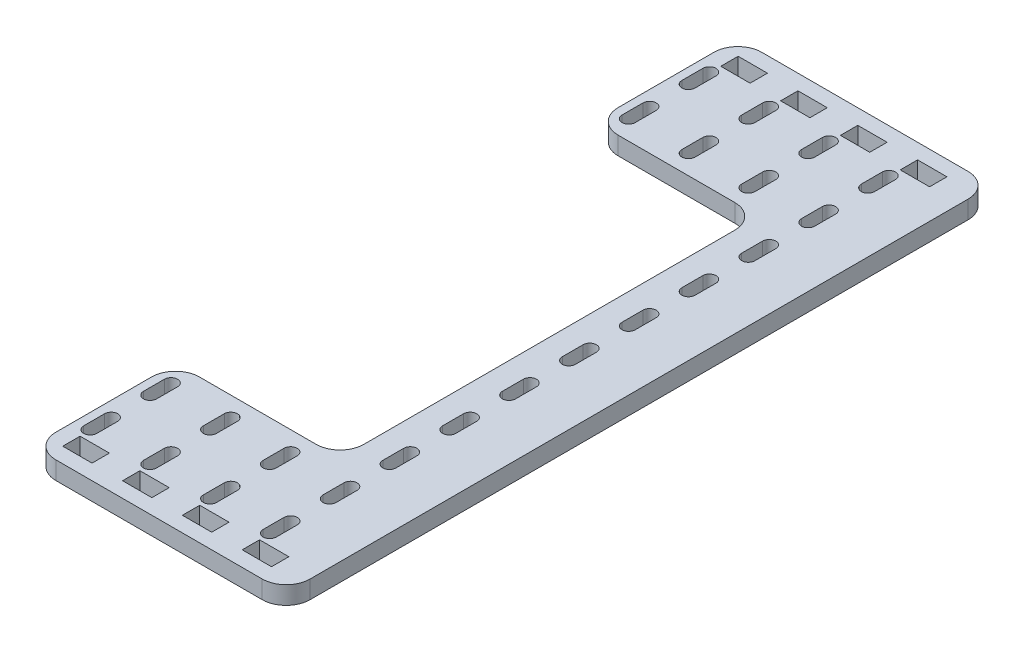
SolidWorks part; units mm, degrees
ref_plane "Front Plane" through (0, 0, 0) normal (0, 0, 1) x (1, 0, 0)
ref_plane "Top Plane" through (0, 0, 0) normal (0, 1, 0) x (1, 0, 0)
ref_plane "Right Plane" through (0, 0, 0) normal (1, 0, 0) x (0, 0, -1)
sketch "Sketch1" plane through (0, 0, 0) normal (0, 1, 0) x (1, 0, 0)
  line L0 (-43.1232, 117.3768) -> (41.8768, 117.3768)
  line L1 (-43.1232, 117.3768) -> (-43.1232, -118.6232)
  line L2 (-43.1232, -118.6232) -> (41.8768, -118.6232)
  line L3 (41.8768, 117.3768) -> (41.8768, -118.6232)
  line L4 (-43.1232, 117.3768) -> (41.8768, -118.6232) construction
  line L5 (-43.1232, -118.6232) -> (41.8768, 117.3768) construction
  point P4 (-0.6232, -0.6232)
extrude "Boss-Extrude1" add sketch "Sketch1" along normal blind 6
sketch "Sketch2" plane through (0, 6, 0) normal (0, 1, 0) x (1, 0, 0)
  line L0 (41.8768, -113.5232) -> (31.8768, -113.5232) construction
  line L1 (41.8768, -118.6232) -> (41.8768, 117.3768) construction
  line L2 (-43.1232, -118.6232) -> (41.8768, -118.6232) construction
  line L3 (11.8768, -107.7232) -> (2.0768, -107.7232)
  line L4 (31.8768, -113.5232) -> (22.0768, -113.5232)
  line L5 (31.8768, -113.5232) -> (31.8768, -107.7232)
  line L6 (31.8768, -107.7232) -> (22.0768, -107.7232)
  line L7 (22.0768, -113.5232) -> (22.0768, -107.7232)
  line L8 (31.8768, -113.5232) -> (22.0768, -107.7232) construction
  line L9 (31.8768, -107.7232) -> (22.0768, -113.5232) construction
  line L10 (2.0768, -113.5232) -> (2.0768, -107.7232)
  line L11 (11.8768, -113.5232) -> (2.0768, -113.5232)
  line L12 (11.8768, -113.5232) -> (11.8768, -107.7232)
  line L13 (-8.1232, -107.7232) -> (-17.9232, -107.7232)
  line L14 (-17.9232, -113.5232) -> (-17.9232, -107.7232)
  line L15 (-8.1232, -113.5232) -> (-17.9232, -113.5232)
  line L16 (-8.1232, -113.5232) -> (-8.1232, -107.7232)
  line L17 (-28.1232, -107.7232) -> (-37.9232, -107.7232)
  line L18 (-37.9232, -113.5232) -> (-37.9232, -107.7232)
  line L19 (-28.1232, -113.5232) -> (-37.9232, -113.5232)
  line L20 (-28.1232, -113.5232) -> (-28.1232, -107.7232)
  point P9 (26.9768, -110.6232)
  dimension "D1" = 10
  dimension "D2" = 5.1
  dimension "D3" = 9.8
  dimension "D4" = 5.8
  dimension "D5" = 4
extrude "Cut-Extrude1" cut sketch "Sketch2" against normal blind 6
ref_plane "Plane1" through (0, 0, 0.6232) normal (0, 0, 1) x (1, 0, 0)
mirror "Mirror2" about plane through (0, 0, 0.6232) normal (0, 0, 1) of "Cut-Extrude1"
sketch "Sketch4" plane through (0, 6, 0) normal (0, 1, 0) x (1, 0, 0)
  line L0 (21.8768, 99.3768) -> (21.8768, 79.3768) construction
  line L1 (21.8768, 99.3768) -> (24.0768, 99.3768) construction
  line L2 (21.8768, 99.3768) -> (19.6768, 99.3768) construction
  line L3 (24.0768, 95.8768) -> (24.0768, 102.8768)
  line L4 (-43.1232, 117.3768) -> (-43.1232, -118.6232) construction
  line L5 (-43.1232, -118.6232) -> (41.8768, -118.6232) construction
  line L6 (41.8768, -118.6232) -> (41.8768, 117.3768) construction
  line L7 (41.8768, 117.3768) -> (-43.1232, 117.3768) construction
  line L8 (19.6768, 95.8768) -> (19.6768, 102.8768)
  line L9 (21.8768, 95.8768) -> (21.8768, 102.8768) construction
  line L10 (4.0768, 95.8768) -> (4.0768, 102.8768)
  line L11 (-0.3232, 95.8768) -> (-0.3232, 102.8768)
  line L12 (-15.9232, 95.8768) -> (-15.9232, 102.8768)
  line L13 (-43.1232, 117.3768) -> (-43.1232, -118.6232) construction
  line L14 (41.8768, 117.3768) -> (-43.1232, 117.3768) construction
  line L15 (-20.3232, 95.8768) -> (-20.3232, 102.8768)
  line L16 (-35.9232, 95.8768) -> (-35.9232, 102.8768)
  line L17 (-40.3232, 95.8768) -> (-40.3232, 102.8768)
  line L18 (4.0768, 75.8768) -> (4.0768, 82.8768)
  line L19 (-0.3232, 75.8768) -> (-0.3232, 82.8768)
  line L20 (-15.9232, 75.8768) -> (-15.9232, 82.8768)
  line L21 (-20.3232, 75.8768) -> (-20.3232, 82.8768)
  line L22 (-35.9232, 75.8768) -> (-35.9232, 82.8768)
  line L23 (-40.3232, 75.8768) -> (-40.3232, 82.8768)
  line L24 (4.0768, 55.8768) -> (4.0768, 62.8768)
  line L25 (-0.3232, 55.8768) -> (-0.3232, 62.8768)
  line L26 (-15.9232, 55.8768) -> (-15.9232, 62.8768)
  line L27 (-20.3232, 55.8768) -> (-20.3232, 62.8768)
  line L28 (-35.9232, 55.8768) -> (-35.9232, 62.8768)
  line L29 (-40.3232, 55.8768) -> (-40.3232, 62.8768)
  line L30 (4.0768, 35.8768) -> (4.0768, 42.8768)
  line L31 (-0.3232, 35.8768) -> (-0.3232, 42.8768)
  line L32 (-15.9232, 35.8768) -> (-15.9232, 42.8768)
  line L33 (-20.3232, 35.8768) -> (-20.3232, 42.8768)
  line L34 (-35.9232, 35.8768) -> (-35.9232, 42.8768)
  line L35 (-40.3232, 35.8768) -> (-40.3232, 42.8768)
  line L36 (4.0768, 15.8768) -> (4.0768, 22.8768)
  line L37 (-0.3232, 15.8768) -> (-0.3232, 22.8768)
  line L38 (-15.9232, 15.8768) -> (-15.9232, 22.8768)
  line L39 (-20.3232, 15.8768) -> (-20.3232, 22.8768)
  line L40 (-35.9232, 15.8768) -> (-35.9232, 22.8768)
  line L41 (-40.3232, 15.8768) -> (-40.3232, 22.8768)
  line L42 (4.0768, -4.1232) -> (4.0768, 2.8768)
  line L43 (-0.3232, -4.1232) -> (-0.3232, 2.8768)
  line L44 (-15.9232, -4.1232) -> (-15.9232, 2.8768)
  line L45 (-20.3232, -4.1232) -> (-20.3232, 2.8768)
  line L46 (-35.9232, -4.1232) -> (-35.9232, 2.8768)
  line L47 (-40.3232, -4.1232) -> (-40.3232, 2.8768)
  line L48 (4.0768, -24.1232) -> (4.0768, -17.1232)
  line L49 (-0.3232, -24.1232) -> (-0.3232, -17.1232)
  line L50 (-15.9232, -24.1232) -> (-15.9232, -17.1232)
  line L51 (-20.3232, -24.1232) -> (-20.3232, -17.1232)
  line L52 (-35.9232, -24.1232) -> (-35.9232, -17.1232)
  line L53 (-40.3232, -24.1232) -> (-40.3232, -17.1232)
  line L54 (4.0768, -44.1232) -> (4.0768, -37.1232)
  line L55 (-0.3232, -44.1232) -> (-0.3232, -37.1232)
  line L56 (-15.9232, -44.1232) -> (-15.9232, -37.1232)
  line L57 (-20.3232, -44.1232) -> (-20.3232, -37.1232)
  line L58 (-35.9232, -44.1232) -> (-35.9232, -37.1232)
  line L59 (-40.3232, -44.1232) -> (-40.3232, -37.1232)
  line L60 (4.0768, -64.1232) -> (4.0768, -57.1232)
  line L61 (-0.3232, -64.1232) -> (-0.3232, -57.1232)
  line L62 (-15.9232, -64.1232) -> (-15.9232, -57.1232)
  line L63 (-20.3232, -64.1232) -> (-20.3232, -57.1232)
  line L64 (-35.9232, -64.1232) -> (-35.9232, -57.1232)
  line L65 (-40.3232, -64.1232) -> (-40.3232, -57.1232)
  line L66 (4.0768, -84.1232) -> (4.0768, -77.1232)
  line L67 (-0.3232, -84.1232) -> (-0.3232, -77.1232)
  line L68 (-15.9232, -84.1232) -> (-15.9232, -77.1232)
  line L69 (-20.3232, -84.1232) -> (-20.3232, -77.1232)
  line L70 (-35.9232, -84.1232) -> (-35.9232, -77.1232)
  line L71 (-40.3232, -84.1232) -> (-40.3232, -77.1232)
  line L72 (4.0768, -104.1232) -> (4.0768, -97.1232)
  line L73 (-0.3232, -104.1232) -> (-0.3232, -97.1232)
  line L74 (-15.9232, -104.1232) -> (-15.9232, -97.1232)
  line L75 (-20.3232, -104.1232) -> (-20.3232, -97.1232)
  line L76 (-35.9232, -104.1232) -> (-35.9232, -97.1232)
  line L77 (-40.3232, -104.1232) -> (-40.3232, -97.1232)
  line L78 (24.0768, 75.8768) -> (24.0768, 82.8768)
  line L79 (19.6768, 75.8768) -> (19.6768, 82.8768)
  line L80 (24.0768, 55.8768) -> (24.0768, 62.8768)
  line L81 (19.6768, 55.8768) -> (19.6768, 62.8768)
  line L82 (24.0768, 35.8768) -> (24.0768, 42.8768)
  line L83 (19.6768, 35.8768) -> (19.6768, 42.8768)
  line L84 (24.0768, 15.8768) -> (24.0768, 22.8768)
  line L85 (19.6768, 15.8768) -> (19.6768, 22.8768)
  line L86 (24.0768, -4.1232) -> (24.0768, 2.8768)
  line L87 (19.6768, -4.1232) -> (19.6768, 2.8768)
  line L88 (24.0768, -24.1232) -> (24.0768, -17.1232)
  line L89 (19.6768, -24.1232) -> (19.6768, -17.1232)
  line L90 (24.0768, -44.1232) -> (24.0768, -37.1232)
  line L91 (19.6768, -44.1232) -> (19.6768, -37.1232)
  line L92 (24.0768, -64.1232) -> (24.0768, -57.1232)
  line L93 (19.6768, -64.1232) -> (19.6768, -57.1232)
  line L94 (24.0768, -84.1232) -> (24.0768, -77.1232)
  line L95 (19.6768, -84.1232) -> (19.6768, -77.1232)
  line L96 (24.0768, -104.1232) -> (24.0768, -97.1232)
  line L97 (19.6768, -104.1232) -> (19.6768, -97.1232)
  arc A2 (19.6768, 102.8768) -> (24.0768, 102.8768) centre (21.8768, 102.8768) cw
  arc A3 (19.6768, 95.8768) -> (24.0768, 95.8768) centre (21.8768, 95.8768) ccw
  arc A4 (-0.3232, 95.8768) -> (4.0768, 95.8768) centre (1.8768, 95.8768) ccw
  arc A5 (-0.3232, 102.8768) -> (4.0768, 102.8768) centre (1.8768, 102.8768) cw
  arc A6 (-20.3232, 95.8768) -> (-15.9232, 95.8768) centre (-18.1232, 95.8768) ccw
  arc A7 (-20.3232, 102.8768) -> (-15.9232, 102.8768) centre (-18.1232, 102.8768) cw
  arc A8 (-40.3232, 95.8768) -> (-35.9232, 95.8768) centre (-38.1232, 95.8768) ccw
  arc A9 (-40.3232, 102.8768) -> (-35.9232, 102.8768) centre (-38.1232, 102.8768) cw
  arc A10 (-0.3232, 75.8768) -> (4.0768, 75.8768) centre (1.8768, 75.8768) ccw
  arc A11 (-0.3232, 82.8768) -> (4.0768, 82.8768) centre (1.8768, 82.8768) cw
  arc A12 (-20.3232, 75.8768) -> (-15.9232, 75.8768) centre (-18.1232, 75.8768) ccw
  arc A13 (-20.3232, 82.8768) -> (-15.9232, 82.8768) centre (-18.1232, 82.8768) cw
  arc A14 (-40.3232, 75.8768) -> (-35.9232, 75.8768) centre (-38.1232, 75.8768) ccw
  arc A15 (-40.3232, 82.8768) -> (-35.9232, 82.8768) centre (-38.1232, 82.8768) cw
  arc A16 (-0.3232, 55.8768) -> (4.0768, 55.8768) centre (1.8768, 55.8768) ccw
  arc A17 (-0.3232, 62.8768) -> (4.0768, 62.8768) centre (1.8768, 62.8768) cw
  arc A18 (-20.3232, 55.8768) -> (-15.9232, 55.8768) centre (-18.1232, 55.8768) ccw
  arc A19 (-20.3232, 62.8768) -> (-15.9232, 62.8768) centre (-18.1232, 62.8768) cw
  arc A20 (-40.3232, 55.8768) -> (-35.9232, 55.8768) centre (-38.1232, 55.8768) ccw
  arc A21 (-40.3232, 62.8768) -> (-35.9232, 62.8768) centre (-38.1232, 62.8768) cw
  arc A22 (-0.3232, 35.8768) -> (4.0768, 35.8768) centre (1.8768, 35.8768) ccw
  arc A23 (-0.3232, 42.8768) -> (4.0768, 42.8768) centre (1.8768, 42.8768) cw
  arc A24 (-20.3232, 35.8768) -> (-15.9232, 35.8768) centre (-18.1232, 35.8768) ccw
  arc A25 (-20.3232, 42.8768) -> (-15.9232, 42.8768) centre (-18.1232, 42.8768) cw
  arc A26 (-40.3232, 35.8768) -> (-35.9232, 35.8768) centre (-38.1232, 35.8768) ccw
  arc A27 (-40.3232, 42.8768) -> (-35.9232, 42.8768) centre (-38.1232, 42.8768) cw
  arc A28 (-0.3232, 15.8768) -> (4.0768, 15.8768) centre (1.8768, 15.8768) ccw
  arc A29 (-0.3232, 22.8768) -> (4.0768, 22.8768) centre (1.8768, 22.8768) cw
  arc A30 (-20.3232, 15.8768) -> (-15.9232, 15.8768) centre (-18.1232, 15.8768) ccw
  arc A31 (-20.3232, 22.8768) -> (-15.9232, 22.8768) centre (-18.1232, 22.8768) cw
  arc A32 (-40.3232, 15.8768) -> (-35.9232, 15.8768) centre (-38.1232, 15.8768) ccw
  arc A33 (-40.3232, 22.8768) -> (-35.9232, 22.8768) centre (-38.1232, 22.8768) cw
  arc A34 (-0.3232, -4.1232) -> (4.0768, -4.1232) centre (1.8768, -4.1232) ccw
  arc A35 (-0.3232, 2.8768) -> (4.0768, 2.8768) centre (1.8768, 2.8768) cw
  arc A36 (-20.3232, -4.1232) -> (-15.9232, -4.1232) centre (-18.1232, -4.1232) ccw
  arc A37 (-20.3232, 2.8768) -> (-15.9232, 2.8768) centre (-18.1232, 2.8768) cw
  arc A38 (-40.3232, -4.1232) -> (-35.9232, -4.1232) centre (-38.1232, -4.1232) ccw
  arc A39 (-40.3232, 2.8768) -> (-35.9232, 2.8768) centre (-38.1232, 2.8768) cw
  arc A40 (-0.3232, -24.1232) -> (4.0768, -24.1232) centre (1.8768, -24.1232) ccw
  arc A41 (-0.3232, -17.1232) -> (4.0768, -17.1232) centre (1.8768, -17.1232) cw
  arc A42 (-20.3232, -24.1232) -> (-15.9232, -24.1232) centre (-18.1232, -24.1232) ccw
  arc A43 (-20.3232, -17.1232) -> (-15.9232, -17.1232) centre (-18.1232, -17.1232) cw
  arc A44 (-40.3232, -24.1232) -> (-35.9232, -24.1232) centre (-38.1232, -24.1232) ccw
  arc A45 (-40.3232, -17.1232) -> (-35.9232, -17.1232) centre (-38.1232, -17.1232) cw
  arc A46 (-0.3232, -44.1232) -> (4.0768, -44.1232) centre (1.8768, -44.1232) ccw
  arc A47 (-0.3232, -37.1232) -> (4.0768, -37.1232) centre (1.8768, -37.1232) cw
  arc A48 (-20.3232, -44.1232) -> (-15.9232, -44.1232) centre (-18.1232, -44.1232) ccw
  arc A49 (-20.3232, -37.1232) -> (-15.9232, -37.1232) centre (-18.1232, -37.1232) cw
  arc A50 (-40.3232, -44.1232) -> (-35.9232, -44.1232) centre (-38.1232, -44.1232) ccw
  arc A51 (-40.3232, -37.1232) -> (-35.9232, -37.1232) centre (-38.1232, -37.1232) cw
  arc A52 (-0.3232, -64.1232) -> (4.0768, -64.1232) centre (1.8768, -64.1232) ccw
  arc A53 (-0.3232, -57.1232) -> (4.0768, -57.1232) centre (1.8768, -57.1232) cw
  arc A54 (-20.3232, -64.1232) -> (-15.9232, -64.1232) centre (-18.1232, -64.1232) ccw
  arc A55 (-20.3232, -57.1232) -> (-15.9232, -57.1232) centre (-18.1232, -57.1232) cw
  arc A56 (-40.3232, -64.1232) -> (-35.9232, -64.1232) centre (-38.1232, -64.1232) ccw
  arc A57 (-40.3232, -57.1232) -> (-35.9232, -57.1232) centre (-38.1232, -57.1232) cw
  arc A58 (-0.3232, -84.1232) -> (4.0768, -84.1232) centre (1.8768, -84.1232) ccw
  arc A59 (-0.3232, -77.1232) -> (4.0768, -77.1232) centre (1.8768, -77.1232) cw
  arc A60 (-20.3232, -84.1232) -> (-15.9232, -84.1232) centre (-18.1232, -84.1232) ccw
  arc A61 (-20.3232, -77.1232) -> (-15.9232, -77.1232) centre (-18.1232, -77.1232) cw
  arc A62 (-40.3232, -84.1232) -> (-35.9232, -84.1232) centre (-38.1232, -84.1232) ccw
  arc A63 (-40.3232, -77.1232) -> (-35.9232, -77.1232) centre (-38.1232, -77.1232) cw
  arc A64 (-0.3232, -104.1232) -> (4.0768, -104.1232) centre (1.8768, -104.1232) ccw
  arc A65 (-0.3232, -97.1232) -> (4.0768, -97.1232) centre (1.8768, -97.1232) cw
  arc A66 (-20.3232, -104.1232) -> (-15.9232, -104.1232) centre (-18.1232, -104.1232) ccw
  arc A67 (-20.3232, -97.1232) -> (-15.9232, -97.1232) centre (-18.1232, -97.1232) cw
  arc A68 (-40.3232, -104.1232) -> (-35.9232, -104.1232) centre (-38.1232, -104.1232) ccw
  arc A69 (-40.3232, -97.1232) -> (-35.9232, -97.1232) centre (-38.1232, -97.1232) cw
  arc A70 (19.6768, 75.8768) -> (24.0768, 75.8768) centre (21.8768, 75.8768) ccw
  arc A71 (19.6768, 82.8768) -> (24.0768, 82.8768) centre (21.8768, 82.8768) cw
  arc A72 (19.6768, 55.8768) -> (24.0768, 55.8768) centre (21.8768, 55.8768) ccw
  arc A73 (19.6768, 62.8768) -> (24.0768, 62.8768) centre (21.8768, 62.8768) cw
  arc A74 (19.6768, 35.8768) -> (24.0768, 35.8768) centre (21.8768, 35.8768) ccw
  arc A75 (19.6768, 42.8768) -> (24.0768, 42.8768) centre (21.8768, 42.8768) cw
  arc A76 (19.6768, 15.8768) -> (24.0768, 15.8768) centre (21.8768, 15.8768) ccw
  arc A77 (19.6768, 22.8768) -> (24.0768, 22.8768) centre (21.8768, 22.8768) cw
  arc A78 (19.6768, -4.1232) -> (24.0768, -4.1232) centre (21.8768, -4.1232) ccw
  arc A79 (19.6768, 2.8768) -> (24.0768, 2.8768) centre (21.8768, 2.8768) cw
  arc A80 (19.6768, -24.1232) -> (24.0768, -24.1232) centre (21.8768, -24.1232) ccw
  arc A81 (19.6768, -17.1232) -> (24.0768, -17.1232) centre (21.8768, -17.1232) cw
  arc A82 (19.6768, -44.1232) -> (24.0768, -44.1232) centre (21.8768, -44.1232) ccw
  arc A83 (19.6768, -37.1232) -> (24.0768, -37.1232) centre (21.8768, -37.1232) cw
  arc A84 (19.6768, -64.1232) -> (24.0768, -64.1232) centre (21.8768, -64.1232) ccw
  arc A85 (19.6768, -57.1232) -> (24.0768, -57.1232) centre (21.8768, -57.1232) cw
  arc A86 (19.6768, -84.1232) -> (24.0768, -84.1232) centre (21.8768, -84.1232) ccw
  arc A87 (19.6768, -77.1232) -> (24.0768, -77.1232) centre (21.8768, -77.1232) cw
  arc A88 (19.6768, -104.1232) -> (24.0768, -104.1232) centre (21.8768, -104.1232) ccw
  arc A89 (19.6768, -97.1232) -> (24.0768, -97.1232) centre (21.8768, -97.1232) cw
  point P10 (24.0768, 99.3768)
  point P13 (19.6768, 99.3768)
  point P22 (21.8768, 99.3768)
  dimension "D7" = 17.8
  dimension "D9" = 20
  dimension "D1" = 2.2
  dimension "D2" = 2.2
  dimension "D3" = 7
  dimension "D4" = 7
  dimension "D5" = 85
  dimension "D6" = 236
  dimension "D8" = 18
  dimension "D10" = 4
  dimension "D11" = 11
extrude "Cut-Extrude2" cut sketch "Sketch4" against normal through all contours L8 A3 L3 A2 | A71 L79 A70 L78 | A73 L81 A72 L80 | A75 L83 A74 L82 | A23 L31 A22 L30 | A17 L25 A16 L24 | A11 L19 A10 L18 | A5 L11 A4 L10 | A13 L21 A12 L20 | A7 L15 A6 L12 | A19 L27 A18 L26 | A25 L33 A24 L32 | A31 L39 A30 L38 | A29 L37 A28 L36 | A77 L85 A76 L84 | A35 L43 A34 L42 | A37 L45 A36 L44 | A33 L41 A32 L40 | A27 L35 A26 L34 | A21 L29 A20 L28 | A15 L23 A14 L22 | A9 L17 A8 L16 | A79 L87 A78 L86 | A81 L89 A80 L88 | A83 L91 A82 L90 | A47 L55 A46 L54 | A41 L49 A40 L48 | A43 L51 A42 L50 | A49 L57 A48 L56 | A51 L59 A50 L58 | A45 L53 A44 L52 | A39 L47 A38 L46 | A89 L97 A88 L96 | A87 L95 A86 L94 | A85 L93 A84 L92 | A53 L61 A52 L60 | A59 L67 A58 L66 | A65 L73 A64 L72 | A67 L75 A66 L74 | A69 L77 A68 L76 | A63 L71 A62 L70 | A61 L69 A60 L68 | A55 L63 A54 L62 | A57 L65 A56 L64 region at (21.8768, 6, -99.3768) region at (1.8768, 6, -99.3768) region at (-18.1232, 6, -99.3768) region at (-38.1232, 6, -99.3768) region at (1.8768, 6, -79.3768) region at (-18.1232, 6, -79.3768) region at (-38.1232, 6, -79.3768) region at (1.8768, 6, -59.3768) region at (-18.1232, 6, -59.3768) region at (-38.1232, 6, -59.3768) region at (1.8768, 6, -39.3768) region at (-18.1232, 6, -39.3768) region at (-38.1232, 6, -39.3768) region at (1.8768, 6, -19.3768) region at (-18.1232, 6, -19.3768) region at (-38.1232, 6, -19.3768) region at (1.8768, 6, 0.6232) region at (-18.1232, 6, 0.6232) region at (-38.1232, 6, 0.6232) region at (1.8768, 6, 20.6232) region at (-18.1232, 6, 20.6232) region at (-38.1232, 6, 20.6232) region at (1.8768, 6, 40.6232) region at (-18.1232, 6, 40.6232) region at (-38.1232, 6, 40.6232) region at (1.8768, 6, 60.6232) region at (-18.1232, 6, 60.6232) region at (-38.1232, 6, 60.6232) region at (1.8768, 6, 80.6232) region at (-18.1232, 6, 80.6232) region at (-38.1232, 6, 80.6232) region at (1.8768, 6, 100.6232) region at (-18.1232, 6, 100.6232) region at (-38.1232, 6, 100.6232) region at (21.8768, 6, -79.3768) region at (21.8768, 6, -59.3768) region at (21.8768, 6, -39.3768) region at (21.8768, 6, -19.3768) region at (21.8768, 6, 0.6232) region at (21.8768, 6, 20.6232) region at (21.8768, 6, 40.6232) region at (21.8768, 6, 60.6232) region at (21.8768, 6, 80.6232) region at (21.8768, 6, 100.6232)
sketch "Sketch5" plane through (0, 6, 0) normal (0, 1, 0) x (1, 0, 0)
  line L0 (-43.1232, 117.3768) -> (-43.1232, -118.6232) construction
  line L1 (-43.1232, 69.3768) -> (11.8768, 69.3768)
  line L2 (-43.1232, 69.3768) -> (-43.1232, -70.6232)
  line L3 (-43.1232, -70.6232) -> (11.8768, -70.6232)
  line L4 (11.8768, 69.3768) -> (11.8768, -70.6232)
  line L5 (-43.1232, 69.3768) -> (11.8768, -70.6232) construction
  line L6 (-43.1232, -70.6232) -> (11.8768, 69.3768) construction
  line L7 (41.8768, 117.3768) -> (-43.1232, 117.3768) construction
  line L8 (-43.1232, -118.6232) -> (41.8768, -118.6232) construction
  line L9 (19.6768, 59.3768) -> (11.8768, 59.3768) construction
  line L10 (19.6768, 55.8768) -> (19.6768, 62.8768) construction
  point P4 (-15.6232, -0.6232)
  dimension "D1" = 48
  dimension "D2" = 48
  dimension "D3" = 7.8
extrude "Cut-Extrude3" cut sketch "Sketch5" against normal through all
fillet "Fillet1" radius 8 8 edges at (41.8768, 3, -117.3768) (11.8768, 3, -69.3768) (11.8768, 3, 70.6232) (41.8768, 3, 118.6232) (-43.1232, 3, 118.6232) (-43.1232, 3, 70.6232) (-43.1232, 3, -117.3768) (-43.1232, 3, -69.3768)
sketch "Sketch6" plane through (0, 6, 0) normal (0, 1, 0) x (1, 0, 0)
  line L0 (-37.9232, 112.2768) -> (-28.1232, 112.2768)
  line L1 (24.0768, 75.8768) -> (24.0768, 82.8768) construction
  line L2 (19.6768, 75.8768) -> (19.6768, 82.8768) construction
  line L3 (24.0768, 95.8768) -> (24.0768, 102.8768) construction
  line L4 (19.6768, 95.8768) -> (19.6768, 102.8768) construction
  line L5 (4.0768, 95.8768) -> (4.0768, 102.8768) construction
  line L6 (-0.3232, 95.8768) -> (-0.3232, 102.8768) construction
  line L7 (4.0768, 75.8768) -> (4.0768, 82.8768) construction
  line L8 (-0.3232, 75.8768) -> (-0.3232, 82.8768) construction
  line L9 (24.0768, 75.8768) -> (24.0768, 82.8768)
  line L10 (19.6768, 75.8768) -> (19.6768, 82.8768)
  line L11 (24.0768, 95.8768) -> (24.0768, 102.8768)
  line L12 (19.6768, 95.8768) -> (19.6768, 102.8768)
  line L13 (4.0768, 95.8768) -> (4.0768, 102.8768)
  line L14 (-0.3232, 95.8768) -> (-0.3232, 102.8768)
  line L15 (4.0768, 75.8768) -> (4.0768, 82.8768)
  line L16 (-0.3232, 75.8768) -> (-0.3232, 82.8768)
  line L17 (21.8768, 105.0768) -> (21.8768, -26.3232)
  arc A0 (19.6768, 75.8768) -> (24.0768, 75.8768) centre (21.8768, 75.8768) ccw construction
  arc A1 (24.0768, 82.8768) -> (19.6768, 82.8768) centre (21.8768, 82.8768) ccw construction
  arc A2 (19.6768, 95.8768) -> (24.0768, 95.8768) centre (21.8768, 95.8768) ccw construction
  arc A3 (24.0768, 102.8768) -> (19.6768, 102.8768) centre (21.8768, 102.8768) ccw construction
  arc A4 (4.0768, 102.8768) -> (-0.3232, 102.8768) centre (1.8768, 102.8768) ccw construction
  arc A5 (-0.3232, 95.8768) -> (4.0768, 95.8768) centre (1.8768, 95.8768) ccw construction
  arc A6 (-0.3232, 75.8768) -> (4.0768, 75.8768) centre (1.8768, 75.8768) ccw construction
  arc A7 (4.0768, 82.8768) -> (-0.3232, 82.8768) centre (1.8768, 82.8768) ccw construction
  arc A8 (19.6768, 75.8768) -> (24.0768, 75.8768) centre (21.8768, 75.8768) ccw
  arc A9 (24.0768, 82.8768) -> (19.6768, 82.8768) centre (21.8768, 82.8768) ccw
  arc A10 (19.6768, 95.8768) -> (24.0768, 95.8768) centre (21.8768, 95.8768) ccw
  arc A11 (24.0768, 102.8768) -> (19.6768, 102.8768) centre (21.8768, 102.8768) ccw
  arc A12 (4.0768, 102.8768) -> (-0.3232, 102.8768) centre (1.8768, 102.8768) ccw
  arc A13 (-0.3232, 95.8768) -> (4.0768, 95.8768) centre (1.8768, 95.8768) ccw
  arc A14 (-0.3232, 75.8768) -> (4.0768, 75.8768) centre (1.8768, 75.8768) ccw
  arc A15 (4.0768, 82.8768) -> (-0.3232, 82.8768) centre (1.8768, 82.8768) ccw
  arc A16 (19.6768, -24.1232) -> (24.0768, -24.1232) centre (21.8768, -24.1232) ccw construction
